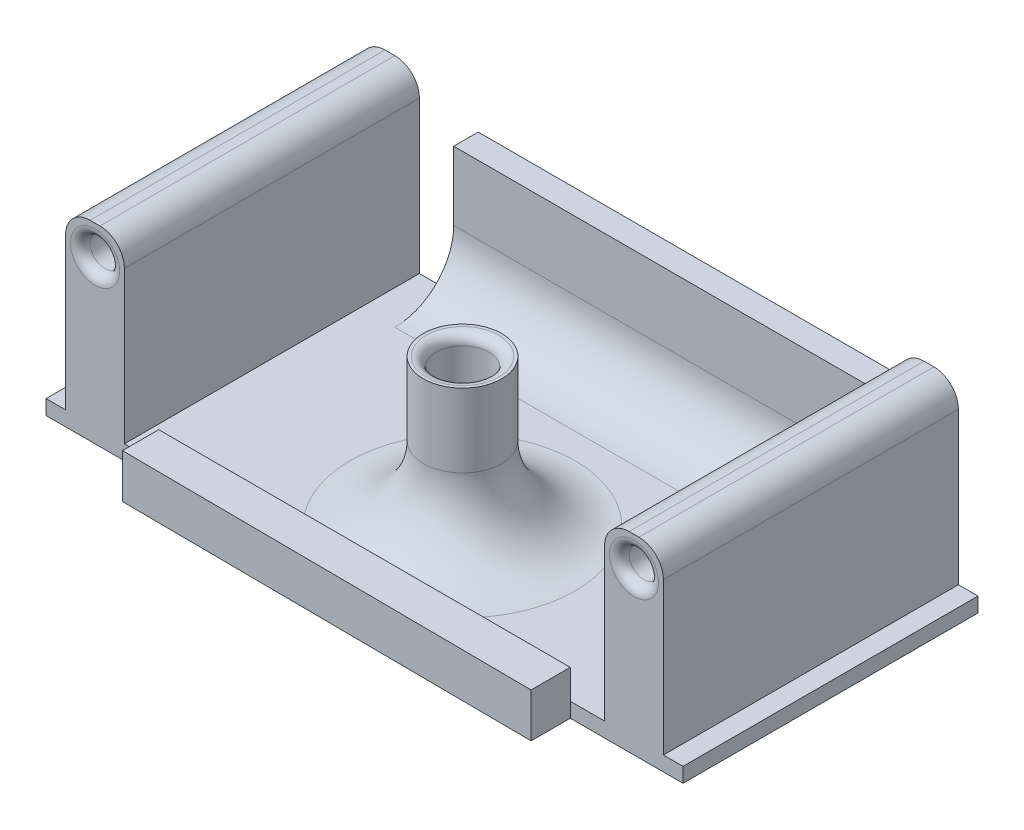
SolidWorks part; units mm, degrees
note: The reader was unsure of these and kept them because the rebuilt part matched: shared geometry of "Эскиз8<3>".
ref_plane "Спереди" through (0, 0, 0) normal (0, 0, 1) x (1, 0, 0)
ref_plane "Сверху" through (0, 0, 0) normal (0, 1, 0) x (1, 0, 0)
ref_plane "Справа" through (0, 0, 0) normal (1, 0, 0) x (0, 0, -1)
sketch "Эскиз1" plane through (0, 0, 0) normal (0, 1, 0) x (1, 0, 0)
  line L1 (-65, -30.1) -> (65, -30.1)
  line L2 (-65, -30.1) -> (-65, 30.1)
  line L3 (-65, 30.1) -> (65, 30.1)
  line L4 (65, -30.1) -> (65, 30.1)
  line L5 (0, 30.1) -> (0, -30.1) construction
  line L6 (-65, 0) -> (65, 0) construction
  point P0 (0, 0)
  dimension "D1" = 60.2
  dimension "D2" = 130
extrude "Бобышка-Вытянуть1" add sketch "Эскиз1" along normal blind 4
sketch "Эскиз2" plane through (0, 4, 0) normal (0, 1, 0) x (1, 0, 0)
  line L0 (65, 30.1) -> (-65, 30.1) construction
  line L1 (-61, -30.1) -> (-49, -30.1)
  line L2 (-61, -30.1) -> (-61, 30.1)
  line L3 (-61, 30.1) -> (-49, 30.1)
  line L4 (-49, -30.1) -> (-49, 30.1)
  line L5 (-55, 30.1) -> (-55, -30.1) construction
  line L6 (-61, 0) -> (-49, 0) construction
  line L7 (0, 38.3989) -> (0, -39.6744) construction
  line L8 (61, 30.1) -> (49, 30.1)
  line L9 (49, -30.1) -> (49, 30.1)
  line L10 (61, -30.1) -> (49, -30.1)
  line L11 (61, -30.1) -> (61, 30.1)
  point P0 (-55, 0)
  dimension "D1" = 55
  dimension "D2" = 12
extrude "Бобышка-Вытянуть2" add sketch "Эскиз2" along normal blind 36
sketch "Эскиз4" plane through (0, 0, 30.1) normal (0, 0, 1) x (1, 0, 0)
  line L0 (-55, 40) -> (-55, -5.1881) construction
  line L1 (-61, 40) -> (-49, 40) construction
  line L2 (0, 51.4646) -> (0, -25.677) construction
  line L3 (-65, 0) -> (65, 0) construction
  circle A0 centre (-55, 34) radius 3
  circle A1 centre (55, 34) radius 3
  dimension "D1" = 6
  dimension "D2" = 34
extrude "Вырез-Вытянуть1" cut sketch "Эскиз4" against normal through all
fillet "Скругление1" radius 5 4 edges at (61, 40, 0) (49, 40, 0) (-49, 40, 0) (-61, 40, 0)
sketch "Эскиз5" plane through (0, 4, 0) normal (0, 1, 0) x (1, 0, 0)
  line L0 (0, 45.2463) -> (0, -39.6744) construction
  line L2 (-49, -30.1) -> (49, -30.1) construction
  circle A0 centre (0, -10.1) radius 8
  dimension "D1" = 20
  dimension "D2" = 16
extrude "Бобышка-Вытянуть3" add sketch "Эскиз5" along normal blind 30
sketch "Эскиз6" plane through (0, 34, 0) normal (0, 1, 0) x (1, 0, 0)
  circle A0 centre (0, -10.1) radius 5.4
  dimension "D1" = 10.8
extrude "Вырез-Вытянуть2" cut sketch "Эскиз6" against normal through all
chamfer "Фаска1" [suppressed] distance 1 angle 45
fillet "Скругление3" radius 2 1 edges at (0, 34, 15.5)
sketch "Эскиз8" plane through (0, 0, 0) normal (0, 1, 0) x (1, 0, 0)
  line L0 (49, 30.1) -> (-49, 30.1) construction
  line L1 (-42, 30.1) -> (42, 30.1)
  line L2 (-42, 30.1) -> (-42, 35.1)
  line L3 (-42, 35.1) -> (42, 35.1)
  line L4 (42, 30.1) -> (42, 35.1)
  line L5 (0, 49.3413) -> (0, -35.1766) construction
  line L6 (-69.2456, 0) -> (102.8783, 0) construction
  line L7 (-42, -37.5) -> (42, -38.1)
  line L8 (42, -30.1) -> (42, -38.1)
  line L9 (-42, -30.1) -> (42, -30.1)
  line L10 (-42, -30.1) -> (-42, -37.5)
  point P9 (0, 30.1)
  line M14 (65, -30.1) -> (-65, -30.1)
  line M16 (-65, 30.1) -> (65, 30.1)
  dimension "D1" = 5
  dimension "D2" = 84
  dimension "D3" = 8
extrude "Бобышка-Вытянуть4" add sketch "Эскиз8" along normal blind 30 contours L4 L2 L3 M16
extrude "Бобышка-Вытянуть5" add sketch "Эскиз8<3>" along normal blind 10 contours L10 L8 L7 M14
sketch "Эскиз8<3>" plane through (0, 0, 0) normal (0, 1, 0) x (1, 0, 0) same geometry as "Эскиз8"
chamfer "Фаска2" distance 1 angle 45 13 edges at (53.5, 0, 30.1) (-42, 0, 33.8) (0, 0, 37.8) (42, 0, 34.1) (-53.5, 0, 30.1) (-65, 0, 0) (53.5, 0, -30.1) (65, 0, 0) (0, 0, 15.5) (-53.5, 0, -30.1) (42, 0, -32.6) (-42, 0, -32.6) (0, 0, -35.1)
fillet "Скругление5" radius 2 4 edges at (-52, 34, -30.1) (-52, 34, 30.1) (52, 34, -30.1) (52, 34, 30.1)
fillet "Скругление6" radius 12 1 edges at (0, 4, -30.1)
fillet "Скругление2" radius 15 1 edges at (0, 4, 2.1)
